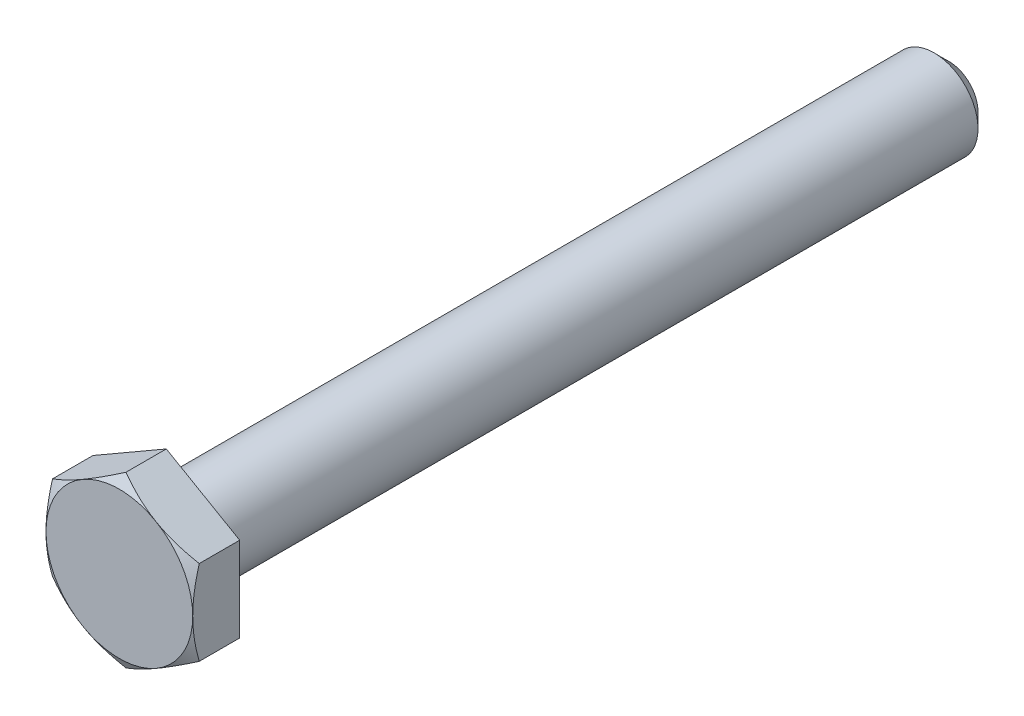
SolidWorks part; units mm, degrees
material "Plain Carbon Steel"
ref_plane "Front" through (0, 0, 0) normal (0, 0, 1) x (1, 0, 0)
ref_plane "Top" through (0, 0, 0) normal (0, 1, 0) x (1, 0, 0)
ref_plane "Right" through (0, 0, 0) normal (1, 0, 0) x (0, 0, -1)
sketch "Sketch1" plane through (0, 0, 0) normal (0, 0, 1) x (1, 0, 0)
  line L1 (-2.3813, -1.3748) -> (0, -2.7496)
  line L2 (0, -2.7496) -> (2.3813, -1.3748)
  line L3 (2.3813, -1.3748) -> (2.3813, 1.3748)
  line L4 (2.3813, 1.3748) -> (0, 2.7496)
  line L5 (0, 2.7496) -> (-2.3813, 1.3748)
  line L6 (-2.3813, 1.3748) -> (-2.3813, -1.3748)
  circle A0 centre (0, 0) radius 2.3813 construction
  circle A1 centre (0, 0) radius 2.3813 construction
  dimension "Head Dia" = 4.7625
extrude "Extrude3" add sketch "Sketch1" along normal blind 1.524
sketch "Sketch4" plane through (0, 0, 0) normal (1, 0, 0) x (0, 0, -1)
  line L0 (0, 0) -> (25.4, 0)
  line L3 (25.4, 0) -> (25.4, 1.4224)
  line L4 (25.4, 1.4224) -> (0, 1.4224)
  line L6 (0, 1.4224) -> (0, 0)
  line L9 (25.4, 1.4224) -> (25.4, -1.4224) construction
  dimension "dia" = 2.8448
  dimension "length" = 25.4
revolve "Revolve1" add sketch "Sketch4" angle 360 about L0
sketch "Sketch13" plane through (0, 0, -25.4) normal (0, 0, -1) x (-1, 0, 0)
  circle A2 centre (0, 0) radius 1.4224
curve "Helix/Spiral1" [suppressed] pitch 0.635 height 26.924 turns 42.4
chamfer "Chamfer2" distance 0.4763 angle 45 1 edges at (1.4224, 0, -25.4)
sketch "Sketch14" plane through (0, 0, 0) normal (1, 0, 0) x (0, 0, -1)
  line L0 (25.4, 1.4422) -> (25.9556, 1.4422)
  line L1 (25.9556, 1.4422) -> (25.7175, 1.0127)
  line L2 (25.7175, 1.0127) -> (25.6381, 1.0127)
  line L3 (25.6381, 1.0127) -> (25.4, 1.4422)
  line L4 (25.5191, 1.2274) -> (25.8366, 1.2274) construction
  dimension "D1" = 0.0794
  dimension "D2" = 58
  dimension "D3" = 0.3175
  dimension "D4" = 0.0198
sweep "Cut-Sweep1" [suppressed] cut profiles "Sketch14" path "Helix/Spiral1"
ref_plane "Plane1" through (0, 0, 12.7) normal (0, 0, -1) x (-1, 0, 0)
sketch "Sketch29" [suppressed] plane through (0, 0, 28.575) normal (0, 0, -1) x (-1, 0, 0)
  circle A0 centre (0, 0) radius 1.7526 construction
  circle A1 centre (0, 0) radius 1.7526
  point P3 (0, -1.7526)
  point P4 (0, 1.7526)
extrude "Extrude11" [suppressed] add sketch "Sketch29" against normal up to surface (28.575 mm away)
sketch "Sketch26" plane through (0, 0, 0) normal (0, 0, 1) x (1, 0, 0)
  circle A1 centre (0, 0) radius 0.5461
  dimension "D1" = 1.0922
extrude "Extrude12" add sketch "Sketch26" along normal up to surface (1.524 mm away) up to face at (0, 0, 1.524)
sketch "Sketch30" plane through (0, 0, 1.524) normal (0, 0, 1) x (1, 0, 0)
  circle A0 centre (0, 0) radius 2.3813 construction
  circle A1 centre (0, 0) radius 2.3813
extrude "Extrude13" cut sketch "Sketch30" against normal blind 2.54 draft 60 flip side to cut
sketch "Sketch18" plane through (0, 0, 0) normal (1, 0, 0) x (0, 0, -1)
  line L1 (25.4, 1.4224) -> (0, 1.4224) construction
  line L2 (-1.524, 2.3813) -> (-1.524, 2.0622) construction
  point P0 (24.4475, -1.4224)
  point P1 (24.765, 1.4224)
  point P2 (-1.524, 2.7496)
  dimension "D1" = 0.635
  dimension "D2" = 0.9525
equation "\"D3@Helix/Spiral1\" = \"Length@Sketch4\" + \"Head Ht@Extrude3\""
equation "\"D1@Sketch14\" = \"D4@Helix/Spiral1\" * .125"
equation "\"D3@Sketch14\" = \"D4@Helix/Spiral1\" * .5"
equation "\"D4@Sketch14\" = \"D1@Sketch14\" * .25"
equation "\"D1@Chamfer2\" = \"D4@Helix/Spiral1\" * .75"
equation "\"D1@Sketch18\" = \"D4@Helix/Spiral1\""
equation "\"D2@Sketch18\" = \"D4@Helix/Spiral1\" * 1.5"
